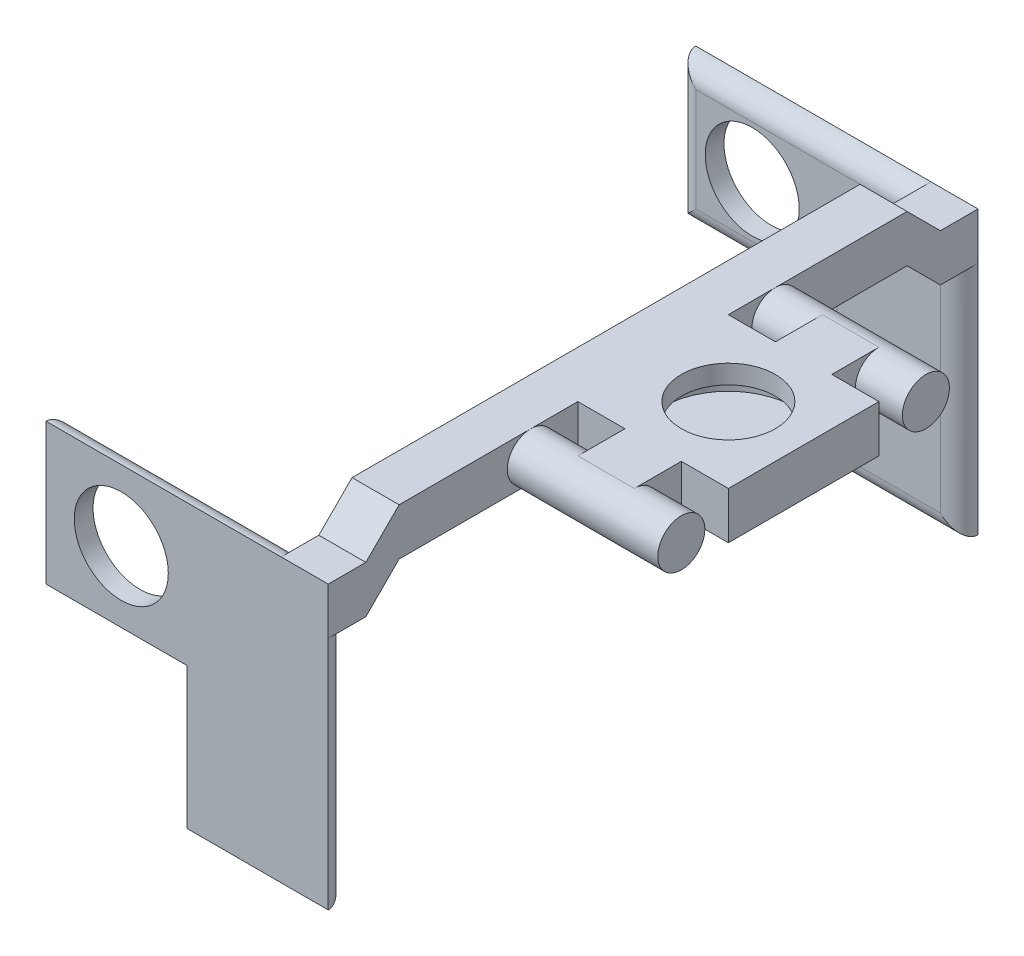
SolidWorks part; units mm, degrees
ref_plane "Front Plane" through (0, 0, 0) normal (0, 0, 1) x (1, 0, 0)
ref_plane "Top Plane" through (0, 0, 0) normal (0, 1, 0) x (1, 0, 0)
ref_plane "Right Plane" through (0, 0, 0) normal (1, 0, 0) x (0, 0, -1)
sketch "Sketch1" plane through (0, 0, 0) normal (0, 1, 0) x (1, 0, 0)
  line L1 (0, 27) -> (-5, 27)
  line L2 (0, 27) -> (0, -27)
  line L3 (0, -27) -> (-5, -27)
  line L4 (-5, 27) -> (-5, -27)
  dimension "D1" = 54
  dimension "D2" = 5
  dimension "D3" = 27
extrude "Boss-Extrude1" add sketch "Sketch1" along normal blind 5
sketch "Sketch3" plane through (0, 0, 0) normal (0, 1, 0) x (1, 0, 0)
  line L0 (0, -27) -> (0, 27) construction
  line L1 (0, -8) -> (16, -8)
  line L2 (0, -8) -> (0, 8)
  line L3 (0, 8) -> (16, 8)
  line L4 (16, -8) -> (16, 8)
  dimension "D1" = 16
  dimension "D2" = 16
  dimension "D3" = 8
extrude "Boss-Extrude2" add sketch "Sketch3" along normal blind 5
sketch "Sketch4" plane through (0, 5, 0) normal (0, 1, 0) x (1, 0, 0)
  circle A0 centre (8, 0) radius 5
  dimension "D1" = 10
sketch "Sketch5" plane through (0, 0, 0) normal (1, 0, 0) x (0, 0, -1)
  line L0 (-27, 5) -> (-30.5355, 1.4645)
  dimension "D1" = 5
sketch "Sketch6" plane through (0, 0, 27) normal (0, 0, 1) x (1, 0, 0)
  line L1 (-5, 5) -> (0, 5)
  line L2 (-5, 5) -> (-5, 0)
  line L3 (-5, 0) -> (0, 0)
  line L4 (0, 5) -> (0, 0)
extrude "Boss-Extrude5" add sketch "Sketch6" along direction (0, -0.7071, 0.7071) on the side of the normal blind 5
sketch "Sketch10" plane through (0, 0, 30.5355) normal (0, 0, 1) x (1, 0, 0)
  line L1 (0, 1.4645) -> (-30, 1.4645)
  line L2 (0, 1.4645) -> (0, -13.5355)
  line L3 (0, -13.5355) -> (-30, -13.5355)
  line L4 (-30, 1.4645) -> (-30, -13.5355)
  dimension "D1" = 15
  dimension "D2" = 30
extrude "Boss-Extrude9" add sketch "Sketch10" along normal blind 4
sketch "Sketch11" plane through (0, 0, 34.5355) normal (0, 0, 1) x (1, 0, 0)
  line L0 (-30, 1.4645) -> (-30, -13.5355) construction
  circle A0 centre (-22, -6.0355) radius 5
  dimension "D1" = 10
  dimension "D2" = 8
sketch "Sketch12" plane through (0, 0, 30.5355) normal (0, 0, -1) x (-1, 0, 0)
  line L0 (30, -13.5355) -> (30, 1.4645)
  line L1 (30, 1.4645) -> (5, 1.4645)
  line L2 (5, 1.4645) -> (5, -3.5355)
  line L3 (5, -3.5355) -> (0, -3.5355)
  line L4 (0, -3.5355) -> (0, -13.5355)
  line L5 (0, -13.5355) -> (30, -13.5355)
extrude "Cut-Extrude1" cut sketch "Sketch12" against normal blind 2
extrude "Cut-Extrude2" cut sketch "Sketch11" against normal up to next
sketch "Sketch13" plane through (0, -13.5355, 0) normal (0, -1, 0) x (1, 0, 0)
  line L0 (0, 32.5355) -> (-30, 32.5355) construction
  line L1 (0, 34.5355) -> (-15, 34.5355)
  line L2 (0, 34.5355) -> (0, 32.5355)
  line L3 (0, 32.5355) -> (-15, 32.5355)
  line L4 (-15, 34.5355) -> (-15, 32.5355)
  dimension "D1" = 15
extrude "Boss-Extrude10" add sketch "Sketch13" along normal blind 15
extrude "Cut-Extrude3" cut sketch "Sketch4" against normal blind 2
sketch "Sketch14" plane through (0, 3, 0) normal (0, 1, 0) x (1, 0, 0)
  circle A0 centre (8, 0) radius 7
  dimension "D1" = 14
extrude "Cut-Extrude4" cut sketch "Sketch14" against normal blind 2
sketch "Sketch16" plane through (0, 0, 8) normal (0, 0, 1) x (1, 0, 0)
  line L0 (0, 5) -> (16, 5) construction
  line L1 (5, 5) -> (11, 5)
  line L2 (5, 5) -> (5, 0)
  line L3 (5, 0) -> (11, 0)
  line L4 (11, 5) -> (11, 0)
  line L5 (0, 0) -> (16, 0) construction
  line L6 (0, 5) -> (0, 0) construction
  dimension "D1" = 6
  dimension "D2" = 5
extrude "Boss-Extrude11" add sketch "Sketch16" along normal blind 5
sketch "Sketch17" plane through (11, 0, 0) normal (1, 0, 0) x (0, 0, -1)
  line L0 (-13, 0) -> (-13, 5) construction
  circle A0 centre (-13, 2.5) radius 2.5
extrude "Boss-Extrude12" add sketch "Sketch17" along normal blind 5 and the other way blind 11
mirror "Mirror2" about plane through (0, 0, 0) normal (0, 0, 1) of "Boss-Extrude12", "Boss-Extrude11", "Boss-Extrude10", "Cut-Extrude2", "Cut-Extrude1", "Boss-Extrude9", "Boss-Extrude5"
fillet "Fillet1" radius 2 12 edges at (0, -16.0355, -32.5355) (0, -16.0355, 32.5355) (-7.5, -28.5355, 32.5355) (-17.5, 1.4645, -32.5355) (-30, -6.0355, -32.5355) (-7.5, -28.5355, -32.5355) (-17.5, 1.4645, 32.5355) (-30, -6.0355, 32.5355)
